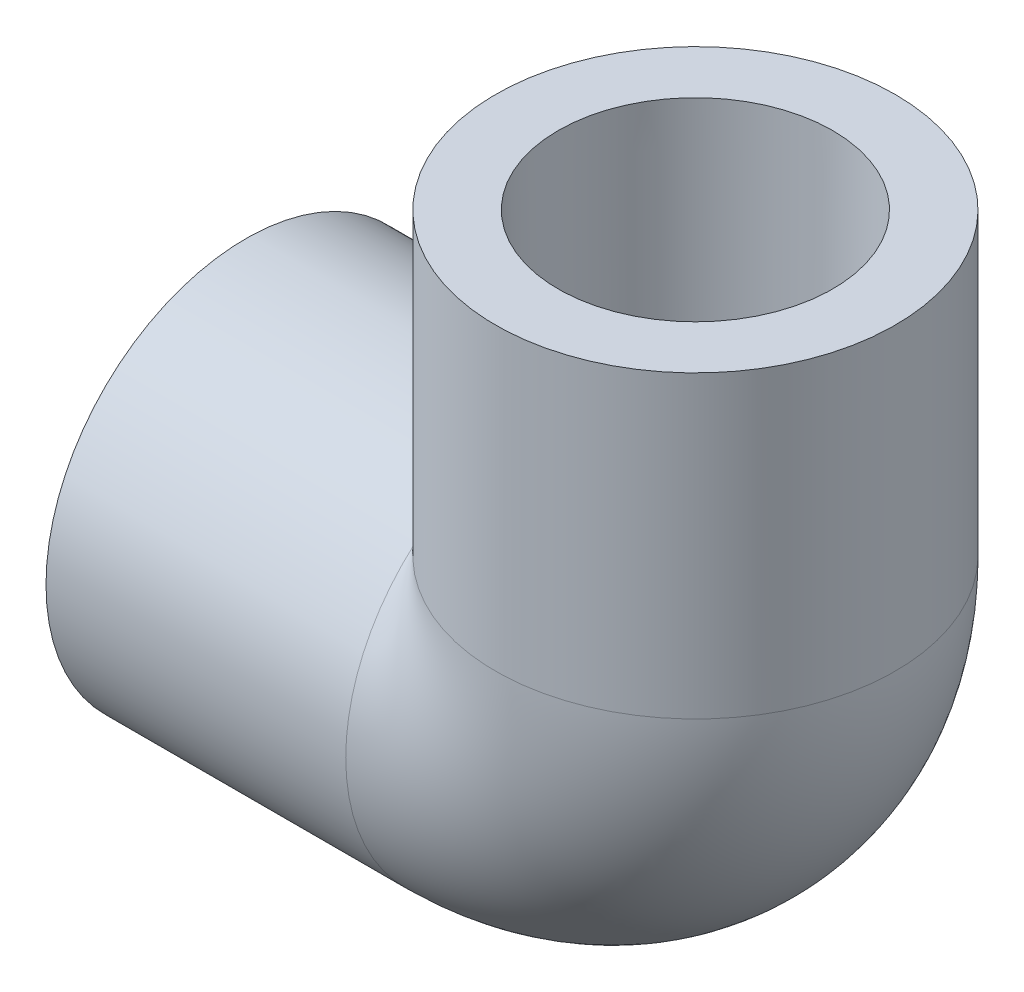
SolidWorks part; units mm, degrees
ref_plane "Front Plane" through (0, 0, 0) normal (0, 0, 1) x (1, 0, 0)
ref_plane "Top Plane" through (0, 0, 0) normal (0, 1, 0) x (1, 0, 0)
ref_plane "Right Plane" through (0, 0, 0) normal (1, 0, 0) x (0, 0, -1)
sketch "Sketch0" plane through (0, 0, 0) normal (0, 0, 1) x (1, 0, 0)
  line L0 (-28.575, 0) -> (0, 0) construction
  line L1 (0, 0) -> (0, 28.575) construction
  line L2 (-9.525, 0) -> (0, 0) construction
  line L3 (0, 0) -> (0, 9.525) construction
  line L4 (-28.575, 12.7) -> (-28.575, -12.7) construction
  line L5 (-9.525, 8.5217) -> (-28.575, 8.7249) construction
  line L6 (-9.525, 8.5217) -> (-9.525, -8.5217) construction
  line L7 (-9.525, -8.5217) -> (-28.575, -8.7249) construction
  line L8 (-28.575, 8.7249) -> (-28.575, -8.7249) construction
  line L9 (-12.7, 28.575) -> (12.7, 28.575) construction
  line L10 (-8.7249, 28.575) -> (8.7249, 28.575) construction
  line L11 (8.7249, 28.575) -> (8.5217, 9.525) construction
  line L12 (8.5217, 9.525) -> (-8.5217, 9.525) construction
  line L13 (-8.5217, 9.525) -> (-8.7249, 28.575) construction
  line L14 (-9.525, 6.2611) -> (-9.525, -6.2611) construction
  line L18 (-6.2611, 9.525) -> (6.2611, 9.525) construction
  dimension "H" = 28.575
  dimension "G" = 9.525
  dimension "M" = 25.4
  dimension "OD A" = 17.4498
  dimension "OD B" = 17.0434
  dimension "ID" = 12.5222
sketch "Sketch1" plane through (0, 0, 0) normal (0, 0, 1) x (1, 0, 0)
  line L0 (-28.575, 0) -> (0, 0) construction
  line L1 (-28.575, 0) -> (0, 0) construction
  line L3 (-28.575, -12.7) -> (-9.525, -12.7)
  line L4 (-28.575, -12.7) -> (-28.575, -8.7249)
  line L5 (-28.575, -8.7249) -> (-9.525, -8.5217)
  line L6 (-9.525, -12.7) -> (-9.525, -8.5217)
revolve "Revolve1" add sketch "Sketch1" angle 360 about L1
sketch "Sketch2" plane through (0, 0, 0) normal (0, 0, 1) x (1, 0, 0)
  line L0 (8.7249, 28.575) -> (8.5217, 9.525)
  line L1 (8.5217, 9.525) -> (12.7, 9.525)
  line L2 (12.7, 9.525) -> (12.7, 28.575)
  line L3 (12.7, 28.575) -> (8.7249, 28.575)
  line L4 (0, 0) -> (0, 28.575) construction
  line L5 (0, 0) -> (0, 28.575) construction
revolve "Revolve2" add sketch "Sketch2" angle 360 about L5
sketch "Sketch3" plane through (-9.525, 0, 0) normal (1, 0, 0) x (0, 0, -1)
  circle A0 centre (0, 0) radius 6.2611
  circle A1 centre (0, 0) radius 12.7
sketch "Sketch4" plane through (0, 0, 0) normal (0, 0, 1) x (1, 0, 0)
  line L0 (-28.575, 0) -> (0, 0) construction
  line L1 (0, 0) -> (0, 28.575) construction
  line L2 (-28.575, 0) -> (-9.525, 0) construction
  line L3 (0, 9.525) -> (0, 28.575) construction
  arc A0 (-9.525, 0) -> (0, 9.525) centre (-9.525, 9.525) ccw
sweep "Sweep1" add profiles "Sketch3" path "Sketch4"
